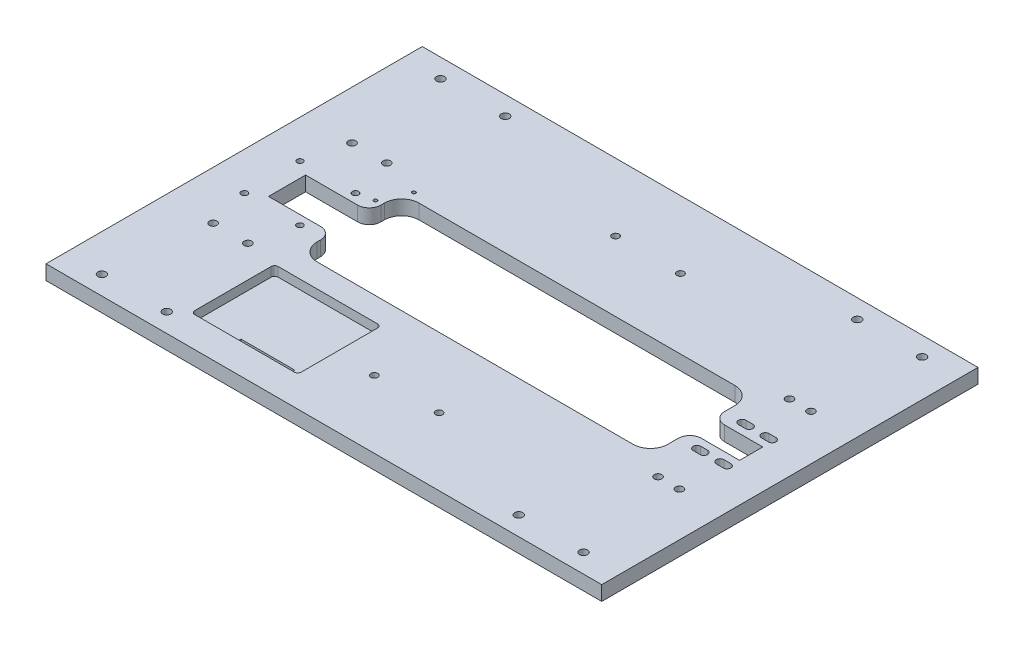
SolidWorks part; units mm, degrees
ref_plane "Front Plane" through (0, 0, 0) normal (0, 0, 1) x (1, 0, 0)
ref_plane "Top Plane" through (0, 0, 0) normal (0, 1, 0) x (1, 0, 0)
ref_plane "Right Plane" through (0, 0, 0) normal (1, 0, 0) x (0, 0, -1)
sketch "Sketch1" plane through (0, 0, 0) normal (0, 1, 0) x (1, 0, 0)
  line L1 (-240, 162.5) -> (240, 162.5)
  line L2 (-240, 162.5) -> (-240, -162.5)
  line L3 (-240, -162.5) -> (240, -162.5)
  line L4 (240, 162.5) -> (240, -162.5)
  line L5 (-240, 162.5) -> (240, -162.5) construction
  line L6 (-240, -162.5) -> (240, 162.5) construction
  point P0 (0, 0)
  dimension "D1" = 480
  dimension "D2" = 325
extrude "Boss-Extrude1" add sketch "Sketch1" along normal blind 12.6
sketch "Sketch2" plane through (0, 0, 0) normal (0, -1, 0) x (1, 0, 0)
  circle A0 centre (41.2474, -104.2) radius 3
  circle A1 centre (-14.7526, -104.2) radius 3
  circle A2 centre (41.2474, 104.2) radius 3
  circle A3 centre (-14.7526, 104.2) radius 3
extrude "Cut-Extrude1" cut sketch "Sketch2" against normal up to next
sketch "Sketch3" plane through (0, 0, 0) normal (0, -1, 0) x (1, 0, 0)
  line L0 (-192.4406, 0) -> (188.5847, 0) construction
  line L1 (163.5847, 44) -> (-139.2887, 44)
  line L2 (163.5847, 44) -> (163.5847, 10)
  line L3 (163.5847, -44) -> (-139.2887, -44)
  line L5 (-139.2887, -44) -> (-139.2887, -16)
  line L6 (-139.2887, -16) -> (-194.2887, -16)
  line L7 (-139.2887, 44) -> (-139.2887, 16)
  line L8 (-139.2887, 16) -> (-194.2887, 16)
  line L9 (-194.2887, 16) -> (-194.2887, -16)
  line L10 (163.5847, 10) -> (206.5847, 10)
  line L11 (206.5847, 10) -> (206.5847, -10)
  line L12 (206.5847, -10) -> (163.5847, -10)
  line L13 (163.5847, -10) -> (163.5847, -44)
  point P0 (0, 0)
  point P1 (-194.2887, 0)
  point P4 (-139.2887, -30)
  dimension "D2" = 55
  dimension "D1" = 16
  dimension "D3" = 10
  dimension "D4" = 10
  dimension "D5" = 43
  dimension "D6" = 28
  dimension "D7" = 28
extrude "Cut-Extrude2" cut sketch "Sketch3" against normal up to next
fillet "Fillet1" radius 10 2 edges at (-139.2887, 6.3, 16) (-139.2887, 6.3, -16)
sketch "Sketch4" plane through (0, 0, 0) normal (0, -1, 0) x (1, 0, 0)
  circle A0 centre (-159.1757, 24) radius 2.6185
  circle A1 centre (-207.1757, 24) radius 2.7
  circle A2 centre (-207.1757, -24) radius 2.5
  circle A3 centre (-159.1757, -24) radius 2.7
  circle A4 centre (-168.1757, -60.0027) radius 3.25
  circle A5 centre (-198.1757, -60.0027) radius 3.25
  circle A6 centre (-168.1757, 60) radius 3.25
  circle A7 centre (-198.1757, 60) radius 3.25
extrude "Cut-Extrude3" cut sketch "Sketch4" against normal up to next
fillet "Fillet2" radius 10 2 edges at (163.5847, 6.3, -10) (163.5847, 6.3, 10)
sketch "Sketch5" plane through (0, 0, 0) normal (0, -1, 0) x (1, 0, 0)
  circle A0 centre (183.6248, 57.5) radius 3.25 construction
  circle A1 centre (202.1353, 57.5) radius 3.25 construction
  circle A2 centre (200.7163, -57.5) radius 3.25 construction
  circle A3 centre (182.2059, -57.5) radius 3.25 construction
  circle A4 centre (183.6248, 57.5) radius 3.25
  circle A5 centre (202.1353, 57.5) radius 3.25
  circle A6 centre (200.7163, -57.5) radius 3.25
  circle A7 centre (182.2059, -57.5) radius 3.25
extrude "Cut-Extrude4" cut sketch "Sketch5" against normal blind 2
extrude "Cut-Extrude5" cut sketch "Sketch5<2>" against normal up to next
sketch "Sketch5<2>" plane through (0, 0, 0) normal (0, -1, 0) x (1, 0, 0) same geometry as "Sketch5"
sketch "Sketch6" plane through (0, 0, 0) normal (0, -1, 0) x (1, 0, 0)
  line L0 (196.0112, -19.5) -> (188.5112, -19.5) construction
  line L1 (196.0112, 19.5) -> (188.5112, 19.5) construction
  line L2 (205.2612, -22.75) -> (199.2612, -22.75)
  line L3 (205.2612, -16.25) -> (199.2612, -16.25)
  line L4 (185.2612, -22.75) -> (179.2612, -22.75)
  line L5 (185.2612, -16.25) -> (179.2612, -16.25)
  line L6 (205.2612, 16.25) -> (199.2612, 16.25)
  line L7 (205.2612, 22.75) -> (199.2612, 22.75)
  line L8 (185.2612, 16.25) -> (179.2612, 16.25)
  line L9 (185.2612, 22.75) -> (179.2612, 22.75)
  line L10 (176.0112, -19.5) -> (171.8318, -19.5) construction
  line L11 (176.0112, 19.5) -> (171.8318, 19.5) construction
  arc A0 (205.2612, -22.75) -> (205.2612, -16.25) centre (205.2612, -19.5) ccw
  arc A1 (185.2612, -22.75) -> (185.2612, -16.25) centre (185.2612, -19.5) ccw
  arc A3 (205.2612, 16.25) -> (205.2612, 22.75) centre (205.2612, 19.5) ccw
  arc A4 (199.2612, -16.25) -> (199.2612, -22.75) centre (199.2612, -19.5) ccw
  arc A7 (179.2612, 22.75) -> (179.2612, 16.25) centre (179.2612, 19.5) ccw
  arc A8 (179.2612, -16.25) -> (179.2612, -22.75) centre (179.2612, -19.5) ccw
  arc A9 (185.2612, 16.25) -> (185.2612, 22.75) centre (185.2612, 19.5) ccw
  arc A10 (199.2612, 22.75) -> (199.2612, 16.25) centre (199.2612, 19.5) ccw
  dimension "D2" = 6.5
  dimension "D3" = 6
  dimension "D7" = 6.5
  dimension "D1" = 6
  dimension "D4" = 6
  dimension "D6" = 6
extrude "Cut-Extrude6" cut sketch "Sketch6" against normal up to next and the other way blind 2
sketch "Sketch7" plane through (0, 12.6, 0) normal (0, 1, 0) x (1, 0, 0)
  circle A0 centre (208, -146.2) radius 2.25
  circle A1 centre (152, -146.2) radius 2.25
  circle A2 centre (-152, -146.2) radius 2.25
  circle A3 centre (-208, -146.2) radius 2.25
  circle A4 centre (-208, 146.2) radius 2.25
  circle A5 centre (-152, 146.2) radius 2.25
  circle A6 centre (208, 146.2) radius 2.25
  circle A7 centre (152, 146.2) radius 2.25
  dimension "D1" = 4.5
extrude "Cut-Extrude7" cut sketch "Sketch7" against normal up to next
sketch "Sketch8" plane through (0, 12.6, 0) normal (0, 1, 0) x (1, 0, 0)
  circle A0 centre (208, 146.2) radius 3.5
  circle A1 centre (152, 146.2) radius 3.5
  circle A2 centre (-152, 146.2) radius 3.5
  circle A3 centre (-208, 146.2) radius 3.5
  circle A4 centre (208, -146.2) radius 3.5
  circle A5 centre (152, -146.2) radius 3.5
  circle A6 centre (-208, -146.2) radius 3.5
  circle A7 centre (-152, -146.2) radius 3.5
  dimension "D1" = 7
extrude "Cut-Extrude8" cut sketch "Sketch8" against normal blind 6
sketch "Sketch9" plane through (0, 12.6, 0) normal (0, 1, 0) x (1, 0, 0)
  line L0 (-139.7386, -65.278) -> (-139.7386, -135.278) construction
  line L1 (-137.7386, -64.278) -> (-51.7386, -64.278)
  line L2 (-140.7386, -67.278) -> (-140.7386, -133.278)
  line L3 (-137.7386, -136.278) -> (-51.7386, -136.278)
  line L4 (-48.7386, -67.278) -> (-48.7386, -133.278)
  line L5 (-49.7386, -135.278) -> (-49.7386, -65.278) construction
  line L6 (-49.7386, -65.278) -> (-139.7386, -65.278) construction
  line L7 (-139.7386, -135.278) -> (-49.7386, -135.278) construction
  arc A0 (-140.7386, -133.278) -> (-137.7386, -136.278) centre (-137.7386, -133.278) ccw
  arc A1 (-51.7386, -136.278) -> (-48.7386, -133.278) centre (-51.7386, -133.278) ccw
  arc A2 (-51.7386, -64.278) -> (-48.7386, -67.278) centre (-51.7386, -67.278) cw
  arc A3 (-137.7386, -64.278) -> (-140.7386, -67.278) centre (-137.7386, -67.278) ccw
  dimension "D5" = 3
  dimension "D1" = 1
  dimension "D2" = 1
  dimension "D3" = 1
  dimension "D4" = 1
extrude "Cut-Extrude9" cut sketch "Sketch9" against normal blind 8
sketch "Sketch10" plane through (0, 4.6, 0) normal (0, 1, 0) x (1, 0, 0)
  line L1 (-107.3842, -126.6207) -> (-60.9487, -126.6207)
  line L2 (-107.3842, -126.6207) -> (-107.3842, -133.6207)
  line L3 (-107.3842, -133.6207) -> (-60.9487, -133.6207)
  line L4 (-60.9487, -126.6207) -> (-60.9487, -133.6207)
  dimension "D1" = 7
extrude "Cut-Extrude10" cut sketch "Sketch10" against normal up to next
sketch "Sketch12" plane through (0, 0, 0) normal (0, -1, 0) x (1, 0, 0)
  circle A0 centre (-145.0986, -27.142) radius 1.5
  circle A1 centre (-134.4986, -49.742) radius 1.5
extrude "Cut-Extrude11" cut sketch "Sketch12" against normal up to next
sketch "Sketch13" plane through (0, 0, 0) normal (0, 1, 0) x (1, 0, 0)
  line L2 (205.2612, 22.75) -> (199.2612, 22.75)
  line L3 (199.2612, 16.25) -> (205.2612, 16.25)
  line L4 (240, -162.5) -> (240, 162.5)
  line L5 (240, 162.5) -> (-240, 162.5)
  line L6 (-240, 162.5) -> (-240, -162.5)
  line L7 (-240, -162.5) -> (240, -162.5)
  line L8 (240, -162.5) -> (240, 162.5)
  line L9 (240, 162.5) -> (-240, 162.5)
  line L10 (-240, 162.5) -> (-240, -162.5)
  line L11 (-240, -162.5) -> (240, -162.5)
  line L12 (205.2612, 22.75) -> (199.2612, 22.75)
  line L13 (199.2612, 16.25) -> (205.2612, 16.25)
  line L14 (205.2612, -16.25) -> (199.2612, -16.25)
  line L15 (199.2612, -22.75) -> (205.2612, -22.75)
  line L16 (205.2612, -16.25) -> (199.2612, -16.25)
  line L17 (199.2612, -22.75) -> (205.2612, -22.75)
  line L18 (163.5847, 20) -> (163.5847, 44)
  line L19 (206.5847, 10) -> (173.5847, 10)
  line L20 (206.5847, -10) -> (206.5847, 10)
  line L21 (173.5847, -10) -> (206.5847, -10)
  line L22 (163.5847, -44) -> (163.5847, -20)
  line L23 (-139.2887, -44) -> (163.5847, -44)
  line L24 (-194.2887, -16) -> (-149.2887, -16)
  line L25 (-194.2887, 16) -> (-194.2887, -16)
  line L26 (-149.2887, 16) -> (-194.2887, 16)
  line L27 (163.5847, 44) -> (-139.2887, 44)
  line L28 (163.5847, 20) -> (163.5847, 44)
  line L29 (206.5847, 10) -> (173.5847, 10)
  line L30 (206.5847, -10) -> (206.5847, 10)
  line L31 (173.5847, -10) -> (206.5847, -10)
  line L32 (163.5847, -44) -> (163.5847, -20)
  line L33 (-139.2887, -44) -> (163.5847, -44)
  line L34 (-194.2887, -16) -> (-149.2887, -16)
  line L35 (-194.2887, 16) -> (-194.2887, -16)
  line L36 (-149.2887, 16) -> (-194.2887, 16)
  line L37 (163.5847, 44) -> (-139.2887, 44)
  line L38 (185.2612, -16.25) -> (179.2612, -16.25)
  line L39 (179.2612, -22.75) -> (185.2612, -22.75)
  line L40 (185.2612, -16.25) -> (179.2612, -16.25)
  line L41 (179.2612, -22.75) -> (185.2612, -22.75)
  line L42 (185.2612, 22.75) -> (179.2612, 22.75)
  line L43 (179.2612, 16.25) -> (185.2612, 16.25)
  line L44 (185.2612, 22.75) -> (179.2612, 22.75)
  line L45 (179.2612, 16.25) -> (185.2612, 16.25)
  line L50 (-137.7386, -136.278) -> (-51.7386, -136.278)
  line L51 (-48.7386, -133.278) -> (-48.7386, -67.278)
  line L52 (-51.7386, -64.278) -> (-137.7386, -64.278)
  line L53 (-140.7386, -67.278) -> (-140.7386, -133.278)
  line L54 (-137.7386, -136.278) -> (-51.7386, -136.278)
  line L55 (-48.7386, -133.278) -> (-48.7386, -67.278)
  line L56 (-51.7386, -64.278) -> (-137.7386, -64.278)
  line L57 (-140.7386, -67.278) -> (-140.7386, -133.278)
  line L58 (-107.3842, -126.6207) -> (-107.3842, -133.6207)
  line L59 (-60.9487, -126.6207) -> (-107.3842, -126.6207)
  line L60 (-60.9487, -133.6207) -> (-60.9487, -126.6207)
  line L61 (-107.3842, -133.6207) -> (-60.9487, -133.6207)
  line L62 (-107.3842, -126.6207) -> (-107.3842, -133.6207)
  line L63 (-60.9487, -126.6207) -> (-107.3842, -126.6207)
  line L64 (-60.9487, -133.6207) -> (-60.9487, -126.6207)
  line L65 (-107.3842, -133.6207) -> (-60.9487, -133.6207)
  line L72 (-139.2887, -26) -> (-139.2887, -44)
  line L73 (-139.2887, -26) -> (-139.2887, -44)
  line L74 (-139.2887, 44) -> (-139.2887, 26)
  line L75 (-139.2887, 44) -> (-139.2887, 26)
  circle A0 centre (202.1353, -57.5) radius 3.25 construction
  circle A1 centre (183.6248, -57.5) radius 3.25 construction
  arc A2 (205.2612, 16.25) -> (205.2612, 22.75) centre (205.2612, 19.5) ccw
  arc A3 (199.2612, 22.75) -> (199.2612, 16.25) centre (199.2612, 19.5) ccw
  arc A4 (163.5847, 20) -> (173.5847, 10) centre (173.5847, 20) ccw
  arc A5 (173.5847, -10) -> (163.5847, -20) centre (173.5847, -20) ccw
  arc A6 (-139.2887, -26) -> (-149.2887, -16) centre (-149.2887, -26) ccw
  arc A7 (-149.2887, 16) -> (-139.2887, 26) centre (-149.2887, 26) ccw
  arc A8 (163.5847, 20) -> (173.5847, 10) centre (173.5847, 20) ccw
  arc A9 (173.5847, -10) -> (163.5847, -20) centre (173.5847, -20) ccw
  arc A10 (-139.2887, -26) -> (-149.2887, -16) centre (-149.2887, -26) ccw
  arc A11 (-149.2887, 16) -> (-139.2887, 26) centre (-149.2887, 26) ccw
  arc A12 (205.2612, 16.25) -> (205.2612, 22.75) centre (205.2612, 19.5) ccw
  arc A13 (199.2612, 22.75) -> (199.2612, 16.25) centre (199.2612, 19.5) ccw
  arc A14 (205.2612, -22.75) -> (205.2612, -16.25) centre (205.2612, -19.5) ccw
  arc A15 (199.2612, -16.25) -> (199.2612, -22.75) centre (199.2612, -19.5) ccw
  arc A16 (205.2612, -22.75) -> (205.2612, -16.25) centre (205.2612, -19.5) ccw
  arc A17 (199.2612, -16.25) -> (199.2612, -22.75) centre (199.2612, -19.5) ccw
  arc A18 (185.2612, -22.75) -> (185.2612, -16.25) centre (185.2612, -19.5) ccw
  arc A19 (179.2612, -16.25) -> (179.2612, -22.75) centre (179.2612, -19.5) ccw
  arc A20 (185.2612, -22.75) -> (185.2612, -16.25) centre (185.2612, -19.5) ccw
  arc A21 (179.2612, -16.25) -> (179.2612, -22.75) centre (179.2612, -19.5) ccw
  arc A22 (185.2612, 16.25) -> (185.2612, 22.75) centre (185.2612, 19.5) ccw
  arc A23 (179.2612, 22.75) -> (179.2612, 16.25) centre (179.2612, 19.5) ccw
  arc A24 (185.2612, 16.25) -> (185.2612, 22.75) centre (185.2612, 19.5) ccw
  arc A25 (179.2612, 22.75) -> (179.2612, 16.25) centre (179.2612, 19.5) ccw
  circle A26 centre (182.2059, 57.5) radius 3.25 construction
  circle A27 centre (200.7163, 57.5) radius 3.25 construction
  circle A28 centre (152, -146.2) radius 2.25 construction
  circle A29 centre (152, -146.2) radius 3.5 construction
  circle A30 centre (208, -146.2) radius 2.25 construction
  circle A31 centre (208, -146.2) radius 3.5 construction
  circle A32 centre (41.2474, -104.2) radius 3 construction
  circle A33 centre (-14.7526, -104.2) radius 3 construction
  circle A34 centre (-152, -146.2) radius 2.25 construction
  circle A35 centre (-152, -146.2) radius 3.5 construction
  circle A36 centre (-208, -146.2) radius 2.25 construction
  circle A37 centre (-208, -146.2) radius 3.5 construction
  circle A38 centre (-198.1757, -60) radius 3.25 construction
  circle A39 centre (-168.1757, -60) radius 3.25 construction
  circle A40 centre (-168.1757, -60) radius 3.25
  circle A41 centre (-198.1757, -60) radius 3.25
  circle A42 centre (-208, -146.2) radius 3.5
  circle A43 centre (-208, -146.2) radius 2.25
  circle A44 centre (-152, -146.2) radius 3.5
  circle A45 centre (-152, -146.2) radius 2.25
  circle A46 centre (-14.7526, -104.2) radius 3
  circle A47 centre (41.2474, -104.2) radius 3
  circle A48 centre (208, -146.2) radius 3.5
  circle A49 centre (208, -146.2) radius 2.25
  circle A50 centre (152, -146.2) radius 3.5
  circle A51 centre (152, -146.2) radius 2.25
  circle A52 centre (200.7163, 57.5) radius 3.25
  circle A53 centre (182.2059, 57.5) radius 3.25
  circle A54 centre (183.6248, -57.5) radius 3.25
  circle A55 centre (202.1353, -57.5) radius 3.25
  circle A56 centre (208, 146.2) radius 3.5 construction
  circle A57 centre (208, 146.2) radius 2.25 construction
  circle A58 centre (152, 146.2) radius 3.5 construction
  circle A59 centre (152, 146.2) radius 2.25 construction
  circle A60 centre (41.2474, 104.2) radius 3 construction
  circle A61 centre (-14.7526, 104.2) radius 3 construction
  circle A62 centre (-152, 146.2) radius 3.5 construction
  circle A63 centre (-152, 146.2) radius 2.25 construction
  circle A64 centre (-208, 146.2) radius 3.5 construction
  circle A65 centre (-208, 146.2) radius 2.25 construction
  circle A66 centre (-198.1757, 60.0027) radius 3.25 construction
  circle A67 centre (-168.1757, 60.0027) radius 3.25 construction
  circle A68 centre (-134.4986, 49.742) radius 1.5 construction
  circle A69 centre (-145.0986, 27.142) radius 1.5 construction
  circle A70 centre (-159.1757, 24) radius 2.7 construction
  circle A71 centre (-207.1757, 24) radius 2.5 construction
  circle A72 centre (-207.1757, -24) radius 2.7 construction
  circle A73 centre (-159.1757, -24) radius 2.6185 construction
  circle A74 centre (208, 146.2) radius 3.5
  circle A75 centre (208, 146.2) radius 2.25
  circle A76 centre (152, 146.2) radius 3.5
  circle A77 centre (152, 146.2) radius 2.25
  circle A78 centre (41.2474, 104.2) radius 3
  circle A79 centre (-14.7526, 104.2) radius 3
  circle A80 centre (-152, 146.2) radius 3.5
  circle A81 centre (-152, 146.2) radius 2.25
  circle A82 centre (-208, 146.2) radius 3.5
  circle A83 centre (-208, 146.2) radius 2.25
  circle A84 centre (-198.1757, 60.0027) radius 3.25
  circle A85 centre (-168.1757, 60.0027) radius 3.25
  circle A86 centre (-134.4986, 49.742) radius 1.5
  circle A87 centre (-145.0986, 27.142) radius 1.5
  circle A88 centre (-159.1757, 24) radius 2.7
  circle A89 centre (-207.1757, 24) radius 2.5
  circle A90 centre (-207.1757, -24) radius 2.7
  circle A91 centre (-159.1757, -24) radius 2.6185
  arc A96 (-140.7386, -133.278) -> (-137.7386, -136.278) centre (-137.7386, -133.278) ccw
  arc A97 (-51.7386, -136.278) -> (-48.7386, -133.278) centre (-51.7386, -133.278) ccw
  arc A98 (-48.7386, -67.278) -> (-51.7386, -64.278) centre (-51.7386, -67.278) ccw
  arc A99 (-137.7386, -64.278) -> (-140.7386, -67.278) centre (-137.7386, -67.278) ccw
  arc A100 (-140.7386, -133.278) -> (-137.7386, -136.278) centre (-137.7386, -133.278) ccw
  arc A101 (-51.7386, -136.278) -> (-48.7386, -133.278) centre (-51.7386, -133.278) ccw
  arc A102 (-48.7386, -67.278) -> (-51.7386, -64.278) centre (-51.7386, -67.278) ccw
  arc A103 (-137.7386, -64.278) -> (-140.7386, -67.278) centre (-137.7386, -67.278) ccw
  dimension "D1" = 0
  dimension "D2" = 0
  dimension "D3" = 0
  dimension "D4" = 0
  dimension "D5" = 0
  dimension "D6" = 0
  dimension "D7" = 0
  dimension "D8" = 0
fillet "Fillet3" radius 15 4 edges at (163.5847, 6.3, 44) (163.5847, 6.3, -44) (-139.2887, 6.3, 44) (-139.2887, 6.3, -44)
